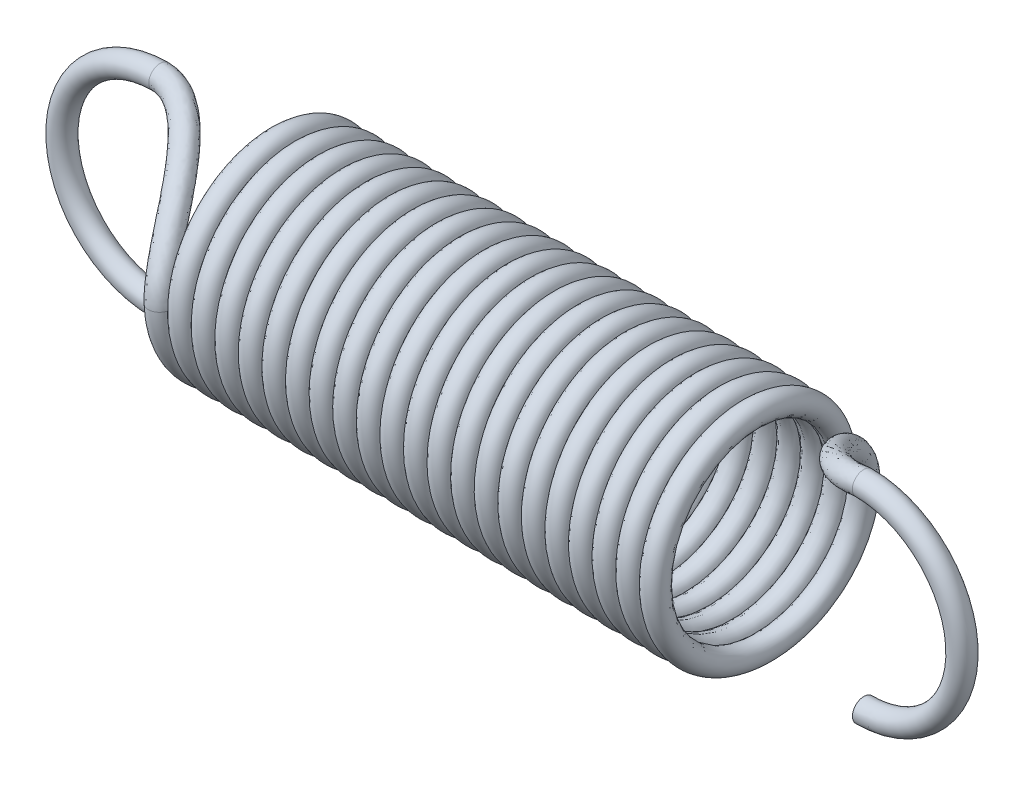
SolidWorks part; units mm, degrees
note: '?' marks a value the reader was unsure of.
ref_plane "Front Plane" through (0, 0, 0) normal (0, 0, 1) x (1, 0, 0)
ref_plane "Top Plane" through (0, 0, 0) normal (0, 1, 0) x (1, 0, 0)
ref_plane "Right Plane" through (0, 0, 0) normal (1, 0, 0) x (0, 0, -1)
sketch "Sketch1" plane through (0, 0, 0) normal (0, 0, 1) x (1, 0, 0)
  line L0 (-13.3604, 0) -> (13.3604, 0) construction
  line L1 (-13.3604, 3.175) -> (-13.3604, -3.175) construction
  line L2 (-13.3604, 0) -> (-12.7, 0) construction
  line L3 (-13.3604, 0) -> (37.4396, 0) construction
  line L5 (-13.3604, -3.175) -> (-13.3604, 3.175) construction
  line L6 (13.3604, 0) -> (-13.3604, 0) construction
  line L7 (37.4396, 0) -> (-13.3604, 0) construction
sketch "Sketch2" plane through (0, 0, 0) normal (0, 0, 1) x (1, 0, 0)
  line L0 (-13.3604, 0) -> (13.3604, 0) construction
  line L1 (-10.1854, 3.175) -> (10.1854, 3.175) construction
  line L2 (-10.1854, 2.5146) -> (10.1854, 2.5146) construction
  line L3 (-10.1854, 0) -> (-10.1854, -2.8448) construction
  line L5 (-10.1854, 2.5146) -> (-10.1854, 3.175) construction
  line L6 (-7.6708, 0) -> (-7.0104, 0) construction
  line L7 (7.6708, 0) -> (7.0104, 0) construction
  circle A0 centre (-10.1854, 0) radius 3.175 construction
  circle A1 centre (-10.1854, 0) radius 2.5146 construction
  arc A2 (-10.1854, 2.8448) -> (-10.1854, -2.8448) centre (-10.1854, 0) ccw
  circle A3 centre (10.1854, 0) radius 3.175 construction
  circle A4 centre (10.1854, 0) radius 2.5146 construction
  point P14 (-10.1854, -2.5146)
  point P24 (-7.3406, 0)
  point P25 (7.3406, 0)
  dimension "D1" = 90
  dimension "D2" = 14.6812
ref_plane "Plane1" through (-7.3406, 0, 0) normal (1, 0, 0) x (0, 0, -1)
sketch "Sketch3" plane through (-7.3406, 0, 0) normal (1, 0, 0) x (0, 0, -1)
  circle A0 centre (0, 0) radius 2.8448
  point P3 (0, 2.8448)
  point P4 (-2.8448, 0)
curve "Helix/Spiral1" pitch 0.6828 height 14.6812 turns 21.5
sketch "Sketch4" plane through (0, 0, 0) normal (0, 0, 1) x (1, 0, 0)
  line L0 (0, 0) -> (0, 3.175) construction
  line L1 (-10.1854, 3.175) -> (10.1854, 3.175) construction
  line L2 (10.1854, 2.5146) -> (10.1854, 3.175) construction
  arc A0 (-10.1854, 2.8448) -> (-10.1854, -2.8448) centre (-10.1854, 0) ccw construction
  arc A1 (-10.1854, 2.8448) -> (-10.1854, -2.8448) centre (-10.1854, 0) ccw construction
  arc A4 (10.1854, 2.8448) -> (10.1854, -2.8448) centre (10.1854, 0) cw
sketch "Sketch5" plane through (0, 0, 0) normal (0, 1, 0) x (1, 0, 0)
  line L0 (-7.3406, 0) -> (-7.3406, -2.8448) construction
  line L1 (-10.1854, 0) -> (-10.1854, -2.8448) construction
  line L3 (7.3406, 0) -> (7.3406, 2.8448) construction
  point P8 (-7.3406, -2.8448)
  point P9 (7.3406, 2.8448)
ref_plane "Plane2" through (-10.1854, 0, 0) normal (-1, 0, 0) x (0, 0, 1)
sketch3d "3DSketch1"
  arc A0 (-10.1854, 2.8448, 0) -> (-10.1854, -2.8448, 0) centre (-10.1854, 0, 0) ccw construction
  arc A1 (-10.1854, 2.8448, 0) -> (-10.1854, -2.8448, 0) centre (-10.1854, 0, 0) ccw construction
  spline S0 degree 3 poles (-10.1854, 2.8448, 0) (-8.5979, 2.8448, 0) (-7.4012, 1.5863, 2.8449) (-7.3406, 0, 2.8448) knots 0 0 0 0 1 1 1 1
  spline S1 degree 3 poles (-7.3406, 0, 2.8448) (-7.3265, -0.37, 2.8448) (-7.2979, -1.1181, 2.6967) (-7.2553, -2.0637, 2.0639) (-7.2126, -2.6968, 1.117) (-7.1699, -2.9188, 0) (-7.1272, -2.6967, -1.117) (-7.0845, -2.0639, -2.0639) (-7.0419, -1.117, -2.6967) (-6.9992, 0, -2.9189) (-6.9565, 1.117, -2.6967) (-6.9138, 2.0639, -2.0639) (-6.8711, 2.6967, -1.117) (-6.8285, 2.9189, 0) (-6.7858, 2.6967, 1.117) (-6.7431, 2.0639, 2.0639) (-6.7004, 1.117, 2.6967) (-6.6578, 0, 2.9189) (-6.6151, -1.117, 2.6967) (-6.5724, -2.0639, 2.0639) (-6.5297, -2.6967, 1.117) (-6.487, -2.9189, 0) (-6.4444, -2.6967, -1.117) (-6.4017, -2.0639, -2.0639) (-6.359, -1.117, -2.6967) (-6.3163, 0, -2.9189) (-6.2737, 1.117, -2.6967) (-6.231, 2.0639, -2.0639) (-6.1883, 2.6967, -1.117) (-6.1456, 2.9189, 0) (-6.1029, 2.6967, 1.117) (-6.0603, 2.0639, 2.0639) (-6.0176, 1.117, 2.6967) (-5.9749, 0, 2.9189) (-5.9322, -1.117, 2.6967) (-5.8896, -2.0639, 2.0639) (-5.8469, -2.6967, 1.117) (-5.8042, -2.9189, 0) (-5.7615, -2.6967, -1.117) (-5.7188, -2.0639, -2.0639) (-5.6762, -1.117, -2.6967) (-5.6335, 0, -2.9189) (-5.5908, 1.117, -2.6967) (-5.5481, 2.0639, -2.0639) (-5.5054, 2.6967, -1.117) (-5.4628, 2.9189, 0) (-5.4201, 2.6967, 1.117) (-5.3774, 2.0639, 2.0639) (-5.3347, 1.117, 2.6967) (-5.2921, 0, 2.9189) (-5.2494, -1.117, 2.6967) (-5.2067, -2.0639, 2.0639) (-5.164, -2.6967, 1.117) (-5.1213, -2.9189, 0) (-5.0787, -2.6967, -1.117) (-5.036, -2.0639, -2.0639) (-4.9933, -1.117, -2.6967) (-4.9506, 0, -2.9189) (-4.908, 1.117, -2.6967) (-4.8653, 2.0639, -2.0639) (-4.8226, 2.6967, -1.117) (-4.7799, 2.9189, 0) (-4.7372, 2.6967, 1.117) (-4.6946, 2.0639, 2.0639) (-4.6519, 1.117, 2.6967) (-4.6092, 0, 2.9189) (-4.5665, -1.117, 2.6967) (-4.5239, -2.0639, 2.0639) (-4.4812, -2.6967, 1.117) (-4.4385, -2.9189, 0) (-4.3958, -2.6967, -1.117) (-4.3531, -2.0639, -2.0639) (-4.3105, -1.117, -2.6967) (-4.2678, 0, -2.9189) (-4.2251, 1.117, -2.6967) (-4.1824, 2.0639, -2.0639) (-4.1398, 2.6967, -1.117) (-4.0971, 2.9189, 0) (-4.0544, 2.6967, 1.117) (-4.0117, 2.0639, 2.0639) (-3.969, 1.117, 2.6967) (-3.9264, 0, 2.9189) (-3.8837, -1.117, 2.6967) (-3.841, -2.0639, 2.0639) (-3.7983, -2.6967, 1.117) (-3.7557, -2.9189, 0) (-3.713, -2.6967, -1.117) (-3.6703, -2.0639, -2.0639) (-3.6276, -1.117, -2.6967) (-3.5849, 0, -2.9189) (-3.5423, 1.117, -2.6967) (-3.4996, 2.0639, -2.0639) (-3.4569, 2.6967, -1.117) (-3.4142, 2.9189, 0) (-3.3716, 2.6967, 1.117) (-3.3289, 2.0639, 2.0639) (-3.2862, 1.117, 2.6967) (-3.2435, 0, 2.9189) (-3.2008, -1.117, 2.6967) (-3.1582, -2.0639, 2.0639) (-3.1155, -2.6967, 1.117) (-3.0728, -2.9189, 0) (-3.0301, -2.6967, -1.117) (-2.9875, -2.0639, -2.0639) (-2.9448, -1.117, -2.6967) (-2.9021, 0, -2.9189) (-2.8594, 1.117, -2.6967) (-2.8167, 2.0639, -2.0639) (-2.7741, 2.6967, -1.117) (-2.7314, 2.9189, 0) (-2.6887, 2.6967, 1.117) (-2.646, 2.0639, 2.0639) (-2.6034, 1.117, 2.6967) (-2.5607, 0, 2.9189) (-2.518, -1.117, 2.6967) (-2.4753, -2.0639, 2.0639) (-2.4326, -2.6967, 1.117) (-2.39, -2.9189, 0) (-2.3473, -2.6967, -1.117) (-2.3046, -2.0639, -2.0639) (-2.2619, -1.117, -2.6967) (-2.2193, 0, -2.9189) (-2.1766, 1.117, -2.6967) (-2.1339, 2.0639, -2.0639) (-2.0912, 2.6967, -1.117) (-2.0485, 2.9189, 0) (-2.0059, 2.6967, 1.117) (-1.9632, 2.0639, 2.0639) (-1.9205, 1.117, 2.6967) (-1.8778, 0, 2.9189) (-1.8351, -1.117, 2.6967) (-1.7925, -2.0639, 2.0639) (-1.7498, -2.6967, 1.117) (-1.7071, -2.9189, 0) (-1.6644, -2.6967, -1.117) (-1.6218, -2.0639, -2.0639) (-1.5791, -1.117, -2.6967) (-1.5364, 0, -2.9189) (-1.4937, 1.117, -2.6967) (-1.451, 2.0639, -2.0639) (-1.4084, 2.6967, -1.117) (-1.3657, 2.9189, 0) (-1.323, 2.6967, 1.117) (-1.2803, 2.0639, 2.0639) (-1.2377, 1.117, 2.6967) (-1.195, 0, 2.9189) (-1.1523, -1.117, 2.6967) (-1.1096, -2.0639, 2.0639) (-1.0669, -2.6967, 1.117) (-1.0243, -2.9189, 0) (-0.9816, -2.6967, -1.117) (-0.9389, -2.0639, -2.0639) (-0.8962, -1.117, -2.6967) (-0.8536, 0, -2.9189) (-0.8109, 1.117, -2.6967) (-0.7682, 2.0639, -2.0639) (-0.7255, 2.6967, -1.117) (-0.6828, 2.9189, 0) (-0.6402, 2.6967, 1.117) (-0.5975, 2.0639, 2.0639) (-0.5548, 1.117, 2.6967) (-0.5121, 0, 2.9189) (-0.4695, -1.117, 2.6967) (-0.4268, -2.0639, 2.0639) (-0.3841, -2.6967, 1.117) (-0.3414, -2.9189, 0) (-0.2987, -2.6967, -1.117) (-0.2561, -2.0639, -2.0639) (-0.2134, -1.117, -2.6967) (-0.1707, 0, -2.9189) (-0.128, 1.117, -2.6967) (-0.0854, 2.0639, -2.0639) (-0.0427, 2.6967, -1.117) (0, 2.9189, 0) (0.0427, 2.6967, 1.117) (0.0854, 2.0639, 2.0639) (0.128, 1.117, 2.6967) (0.1707, 0, 2.9189) (0.2134, -1.117, 2.6967) (0.2561, -2.0639, 2.0639) (0.2987, -2.6967, 1.117) (0.3414, -2.9189, 0) (0.3841, -2.6967, -1.117) (0.4268, -2.0639, -2.0639) (0.4695, -1.117, -2.6967) (0.5121, 0, -2.9189) (0.5548, 1.117, -2.6967) (0.5975, 2.0639, -2.0639) (0.6402, 2.6967, -1.117) (0.6828, 2.9189, 0) (0.7255, 2.6967, 1.117) (0.7682, 2.0639, 2.0639) (0.8109, 1.117, 2.6967) (0.8536, 0, 2.9189) (0.8962, -1.117, 2.6967) (0.9389, -2.0639, 2.0639) (0.9816, -2.6967, 1.117) (1.0243, -2.9189, 0) (1.0669, -2.6967, -1.117) (1.1096, -2.0639, -2.0639) (1.1523, -1.117, -2.6967) (1.195, 0, -2.9189) (1.2377, 1.117, -2.6967) (1.2803, 2.0639, -2.0639) (1.323, 2.6967, -1.117) (1.3657, 2.9189, 0) (1.4084, 2.6967, 1.117) (1.451, 2.0639, 2.0639) (1.4937, 1.117, 2.6967) (1.5364, 0, 2.9189) (1.5791, -1.117, 2.6967) (1.6218, -2.0639, 2.0639) (1.6644, -2.6967, 1.117) (1.7071, -2.9189, 0) (1.7498, -2.6967, -1.117) (1.7925, -2.0639, -2.0639) (1.8351, -1.117, -2.6967) (1.8778, 0, -2.9189) (1.9205, 1.117, -2.6967) (1.9632, 2.0639, -2.0639) (2.0059, 2.6967, -1.117) (2.0485, 2.9189, 0) (2.0912, 2.6967, 1.117) (2.1339, 2.0639, 2.0639) (2.1766, 1.117, 2.6967) (2.2193, 0, 2.9189) (2.2619, -1.117, 2.6967) (2.3046, -2.0639, 2.0639) (2.3473, -2.6967, 1.117) (2.39, -2.9189, 0) (2.4326, -2.6967, -1.117) (2.4753, -2.0639, -2.0639) (2.518, -1.117, -2.6967) (2.5607, 0, -2.9189) (2.6034, 1.117, -2.6967) (2.646, 2.0639, -2.0639) (2.6887, 2.6967, -1.117) (2.7314, 2.9189, 0) (2.7741, 2.6967, 1.117) (2.8167, 2.0639, 2.0639) (2.8594, 1.117, 2.6967) (2.9021, 0, 2.9189) (2.9448, -1.117, 2.6967) (2.9875, -2.0639, 2.0639) (3.0301, -2.6967, 1.117) (3.0728, -2.9189, 0) (3.1155, -2.6967, -1.117) (3.1582, -2.0639, -2.0639) (3.2008, -1.117, -2.6967) (3.2435, 0, -2.9189) (3.2862, 1.117, -2.6967) (3.3289, 2.0639, -2.0639) (3.3716, 2.6967, -1.117) (3.4142, 2.9189, 0) (3.4569, 2.6967, 1.117) (3.4996, 2.0639, 2.0639) (3.5423, 1.117, 2.6967) (3.5849, 0, 2.9189) (3.6276, -1.117, 2.6967) (3.6703, -2.0639, 2.0639) (3.713, -2.6967, 1.117) (3.7557, -2.9189, 0) (3.7983, -2.6967, -1.117) (3.841, -2.0639, -2.0639) (3.8837, -1.117, -2.6967) (3.9264, 0, -2.9189) (3.969, 1.117, -2.6967) (4.0117, 2.0639, -2.0639) (4.0544, 2.6967, -1.117) (4.0971, 2.9189, 0) (4.1398, 2.6967, 1.117) (4.1824, 2.0639, 2.0639) (4.2251, 1.117, 2.6967) (4.2678, 0, 2.9189) (4.3105, -1.117, 2.6967) (4.3531, -2.0639, 2.0639) (4.3958, -2.6967, 1.117) (4.4385, -2.9189, 0) (4.4812, -2.6967, -1.117) (4.5239, -2.0639, -2.0639) (4.5665, -1.117, -2.6967) (4.6092, 0, -2.9189) (4.6519, 1.117, -2.6967) (4.6946, 2.0639, -2.0639) (4.7372, 2.6967, -1.117) (4.7799, 2.9189, 0) (4.8226, 2.6967, 1.117) (4.8653, 2.0639, 2.0639) (4.908, 1.117, 2.6967) (4.9506, 0, 2.9189) (4.9933, -1.117, 2.6967) (5.036, -2.0639, 2.0639) (5.0787, -2.6967, 1.117) (5.1213, -2.9189, 0) (5.164, -2.6967, -1.117) (5.2067, -2.0639, -2.0639) (5.2494, -1.117, -2.6967) (5.2921, 0, -2.9189) (5.3347, 1.117, -2.6967) (5.3774, 2.0639, -2.0639) (5.4201, 2.6967, -1.117) (5.4628, 2.9189, 0) (5.5054, 2.6967, 1.117) (5.5481, 2.0639, 2.0639) (5.5908, 1.117, 2.6967) (5.6335, 0, 2.9189) (5.6762, -1.117, 2.6967) (5.7188, -2.0639, 2.0639) (5.7615, -2.6967, 1.117) (5.8042, -2.9189, 0) (5.8469, -2.6967, -1.117) (5.8896, -2.0639, -2.0639) (5.9322, -1.117, -2.6967) (5.9749, 0, -2.9189) (6.0176, 1.117, -2.6967) (6.0603, 2.0639, -2.0639) (6.1029, 2.6967, -1.117) (6.1456, 2.9189, 0) (6.1883, 2.6967, 1.117) (6.231, 2.0639, 2.0639) (6.2737, 1.117, 2.6967) (6.3163, 0, 2.9189) (6.359, -1.117, 2.6967) (6.4017, -2.0639, 2.0639) (6.4444, -2.6967, 1.117) (6.487, -2.9189, 0) (6.5297, -2.6967, -1.117) (6.5724, -2.0639, -2.0639) (6.6151, -1.117, -2.6967) (6.6578, 0, -2.9189) (6.7004, 1.117, -2.6967) (6.7431, 2.0639, -2.0639) (6.7858, 2.6967, -1.117) (6.8285, 2.9189, 0) (6.8711, 2.6967, 1.117) (6.9138, 2.0639, 2.0639) (6.9565, 1.117, 2.6967) (6.9992, 0, 2.9189) (7.0419, -1.117, 2.6967) (7.0845, -2.0639, 2.0639) (7.1272, -2.6967, 1.117) (7.1699, -2.9188, 0) (7.2126, -2.6968, -1.117) (7.2553, -2.0637, -2.0639) (7.2979, -1.1181, -2.6967) (7.3265, -0.37, -2.8448) (7.3406, 0, -2.8448) knots 0 0 0 0 0.002907 0.005814 0.008721 0.011628 0.014535 0.017442 0.020349 0.023256 0.026163 0.02907 0.031977 0.034884 0.037791 0.040698 0.043605 0.046512 0.049419 0.052326 0.055233 0.05814 0.061047 0.063953 0.06686 0.069767 0.072674 0.075581 0.078488 0.081395 0.084302 0.087209 0.090116 0.093023 0.09593 0.098837 0.101744 0.104651 0.107558 0.110465 0.113372 0.116279 0.119186 0.122093 0.125 0.127907 0.130814 0.133721 0.136628 0.139535 0.142442 0.145349 0.148256 0.151163 0.15407 0.156977 0.159884 0.162791 0.165698 0.168605 0.171512 0.174419 0.177326 0.180233 0.18314 0.186047 0.188953 0.19186 0.194767 0.197674 0.200581 0.203488 0.206395 0.209302 0.212209 0.215116 0.218023 0.22093 0.223837 0.226744 0.229651 0.232558 0.235465 0.238372 0.241279 0.244186 0.247093 0.25 0.252907 0.255814 0.258721 0.261628 0.264535 0.267442 0.270349 0.273256 0.276163 0.27907 0.281977 0.284884 0.287791 0.290698 0.293605 0.296512 0.299419 0.302326 0.305233 0.30814 0.311047 0.313953 0.31686 0.319767 0.322674 0.325581 0.328488 0.331395 0.334302 0.337209 0.340116 0.343023 0.34593 0.348837 0.351744 0.354651 0.357558 0.360465 0.363372 0.366279 0.369186 0.372093 0.375 0.377907 0.380814 0.383721 0.386628 0.389535 0.392442 0.395349 0.398256 0.401163 0.40407 0.406977 0.409884 0.412791 0.415698 0.418605 0.421512 0.424419 0.427326 0.430233 0.43314 0.436047 0.438953 0.44186 0.444767 0.447674 0.450581 0.453488 0.456395 0.459302 0.462209 0.465116 0.468023 0.47093 0.473837 0.476744 0.479651 0.482558 0.485465 0.488372 0.491279 0.494186 0.497093 0.5 0.502907 0.505814 0.508721 0.511628 0.514535 0.517442 0.520349 0.523256 0.526163 0.52907 0.531977 0.534884 0.537791 0.540698 0.543605 0.546512 0.549419 0.552326 0.555233 0.55814 0.561047 0.563953 0.56686 0.569767 0.572674 0.575581 0.578488 0.581395 0.584302 0.587209 0.590116 0.593023 0.59593 0.598837 0.601744 0.604651 0.607558 0.610465 0.613372 0.616279 0.619186 0.622093 0.625 0.627907 0.630814 0.633721 0.636628 0.639535 0.642442 0.645349 0.648256 0.651163 0.65407 0.656977 0.659884 0.662791 0.665698 0.668605 0.671512 0.674419 0.677326 0.680233 0.68314 0.686047 0.688953 0.69186 0.694767 0.697674 0.700581 0.703488 0.706395 0.709302 0.712209 0.715116 0.718023 0.72093 0.723837 0.726744 0.729651 0.732558 0.735465 0.738372 0.741279 0.744186 0.747093 0.75 0.752907 0.755814 0.758721 0.761628 0.764535 0.767442 0.770349 0.773256 0.776163 0.77907 0.781977 0.784884 0.787791 0.790698 0.793605 0.796512 0.799419 0.802326 0.805233 0.80814 0.811047 0.813953 0.81686 0.819767 0.822674 0.825581 0.828488 0.831395 0.834302 0.837209 0.840116 0.843023 0.84593 0.848837 0.851744 0.854651 0.857558 0.860465 0.863372 0.866279 0.869186 0.872093 0.875 0.877907 0.880814 0.883721 0.886628 0.889535 0.892442 0.895349 0.898256 0.901163 0.90407 0.906977 0.909884 0.912791 0.915698 0.918605 0.921512 0.924419 0.927326 0.930233 0.93314 0.936047 0.938953 0.94186 0.944767 0.947674 0.950581 0.953488 0.956395 0.959302 0.962209 0.965116 0.968023 0.97093 0.973837 0.976744 0.979651 0.982558 0.985465 0.988372 0.991279 0.994186 0.997093 1 1 1 1 construction
  point P8 (-10.1854, 0, 2.8448)
  point P13 (-10.1854, 0, 2.8448)
  dimension "D1" = 4.7625
  dimension "D2" = 4.7625
sketch3d "3DSketch2"
  arc A0 (10.1854, 2.8448, 0) -> (10.1854, -2.8448, 0) centre (10.1854, 0, 0) ccw construction
  spline S0 degree 3 poles (7.3406, 0, -2.8448) (7.3982, 1.507, -2.8448) (8.4029, 2.5846, 0) (10.106, 2.8448, 0) (10.1854, 2.8448, 0) knots 0 0 0 0 0.95 1 1 1 1
  spline S1 degree 3 poles (-7.3406, 0, 2.8448) (-7.3265, -0.37, 2.8448) (-7.2979, -1.1181, 2.6967) (-7.2553, -2.0637, 2.0639) (-7.2126, -2.6968, 1.117) (-7.1699, -2.9188, 0) (-7.1272, -2.6967, -1.117) (-7.0845, -2.0639, -2.0639) (-7.0419, -1.117, -2.6967) (-6.9992, 0, -2.9189) (-6.9565, 1.117, -2.6967) (-6.9138, 2.0639, -2.0639) (-6.8711, 2.6967, -1.117) (-6.8285, 2.9189, 0) (-6.7858, 2.6967, 1.117) (-6.7431, 2.0639, 2.0639) (-6.7004, 1.117, 2.6967) (-6.6578, 0, 2.9189) (-6.6151, -1.117, 2.6967) (-6.5724, -2.0639, 2.0639) (-6.5297, -2.6967, 1.117) (-6.487, -2.9189, 0) (-6.4444, -2.6967, -1.117) (-6.4017, -2.0639, -2.0639) (-6.359, -1.117, -2.6967) (-6.3163, 0, -2.9189) (-6.2737, 1.117, -2.6967) (-6.231, 2.0639, -2.0639) (-6.1883, 2.6967, -1.117) (-6.1456, 2.9189, 0) (-6.1029, 2.6967, 1.117) (-6.0603, 2.0639, 2.0639) (-6.0176, 1.117, 2.6967) (-5.9749, 0, 2.9189) (-5.9322, -1.117, 2.6967) (-5.8896, -2.0639, 2.0639) (-5.8469, -2.6967, 1.117) (-5.8042, -2.9189, 0) (-5.7615, -2.6967, -1.117) (-5.7188, -2.0639, -2.0639) (-5.6762, -1.117, -2.6967) (-5.6335, 0, -2.9189) (-5.5908, 1.117, -2.6967) (-5.5481, 2.0639, -2.0639) (-5.5054, 2.6967, -1.117) (-5.4628, 2.9189, 0) (-5.4201, 2.6967, 1.117) (-5.3774, 2.0639, 2.0639) (-5.3347, 1.117, 2.6967) (-5.2921, 0, 2.9189) (-5.2494, -1.117, 2.6967) (-5.2067, -2.0639, 2.0639) (-5.164, -2.6967, 1.117) (-5.1213, -2.9189, 0) (-5.0787, -2.6967, -1.117) (-5.036, -2.0639, -2.0639) (-4.9933, -1.117, -2.6967) (-4.9506, 0, -2.9189) (-4.908, 1.117, -2.6967) (-4.8653, 2.0639, -2.0639) (-4.8226, 2.6967, -1.117) (-4.7799, 2.9189, 0) (-4.7372, 2.6967, 1.117) (-4.6946, 2.0639, 2.0639) (-4.6519, 1.117, 2.6967) (-4.6092, 0, 2.9189) (-4.5665, -1.117, 2.6967) (-4.5239, -2.0639, 2.0639) (-4.4812, -2.6967, 1.117) (-4.4385, -2.9189, 0) (-4.3958, -2.6967, -1.117) (-4.3531, -2.0639, -2.0639) (-4.3105, -1.117, -2.6967) (-4.2678, 0, -2.9189) (-4.2251, 1.117, -2.6967) (-4.1824, 2.0639, -2.0639) (-4.1398, 2.6967, -1.117) (-4.0971, 2.9189, 0) (-4.0544, 2.6967, 1.117) (-4.0117, 2.0639, 2.0639) (-3.969, 1.117, 2.6967) (-3.9264, 0, 2.9189) (-3.8837, -1.117, 2.6967) (-3.841, -2.0639, 2.0639) (-3.7983, -2.6967, 1.117) (-3.7557, -2.9189, 0) (-3.713, -2.6967, -1.117) (-3.6703, -2.0639, -2.0639) (-3.6276, -1.117, -2.6967) (-3.5849, 0, -2.9189) (-3.5423, 1.117, -2.6967) (-3.4996, 2.0639, -2.0639) (-3.4569, 2.6967, -1.117) (-3.4142, 2.9189, 0) (-3.3716, 2.6967, 1.117) (-3.3289, 2.0639, 2.0639) (-3.2862, 1.117, 2.6967) (-3.2435, 0, 2.9189) (-3.2008, -1.117, 2.6967) (-3.1582, -2.0639, 2.0639) (-3.1155, -2.6967, 1.117) (-3.0728, -2.9189, 0) (-3.0301, -2.6967, -1.117) (-2.9875, -2.0639, -2.0639) (-2.9448, -1.117, -2.6967) (-2.9021, 0, -2.9189) (-2.8594, 1.117, -2.6967) (-2.8167, 2.0639, -2.0639) (-2.7741, 2.6967, -1.117) (-2.7314, 2.9189, 0) (-2.6887, 2.6967, 1.117) (-2.646, 2.0639, 2.0639) (-2.6034, 1.117, 2.6967) (-2.5607, 0, 2.9189) (-2.518, -1.117, 2.6967) (-2.4753, -2.0639, 2.0639) (-2.4326, -2.6967, 1.117) (-2.39, -2.9189, 0) (-2.3473, -2.6967, -1.117) (-2.3046, -2.0639, -2.0639) (-2.2619, -1.117, -2.6967) (-2.2193, 0, -2.9189) (-2.1766, 1.117, -2.6967) (-2.1339, 2.0639, -2.0639) (-2.0912, 2.6967, -1.117) (-2.0485, 2.9189, 0) (-2.0059, 2.6967, 1.117) (-1.9632, 2.0639, 2.0639) (-1.9205, 1.117, 2.6967) (-1.8778, 0, 2.9189) (-1.8351, -1.117, 2.6967) (-1.7925, -2.0639, 2.0639) (-1.7498, -2.6967, 1.117) (-1.7071, -2.9189, 0) (-1.6644, -2.6967, -1.117) (-1.6218, -2.0639, -2.0639) (-1.5791, -1.117, -2.6967) (-1.5364, 0, -2.9189) (-1.4937, 1.117, -2.6967) (-1.451, 2.0639, -2.0639) (-1.4084, 2.6967, -1.117) (-1.3657, 2.9189, 0) (-1.323, 2.6967, 1.117) (-1.2803, 2.0639, 2.0639) (-1.2377, 1.117, 2.6967) (-1.195, 0, 2.9189) (-1.1523, -1.117, 2.6967) (-1.1096, -2.0639, 2.0639) (-1.0669, -2.6967, 1.117) (-1.0243, -2.9189, 0) (-0.9816, -2.6967, -1.117) (-0.9389, -2.0639, -2.0639) (-0.8962, -1.117, -2.6967) (-0.8536, 0, -2.9189) (-0.8109, 1.117, -2.6967) (-0.7682, 2.0639, -2.0639) (-0.7255, 2.6967, -1.117) (-0.6828, 2.9189, 0) (-0.6402, 2.6967, 1.117) (-0.5975, 2.0639, 2.0639) (-0.5548, 1.117, 2.6967) (-0.5121, 0, 2.9189) (-0.4695, -1.117, 2.6967) (-0.4268, -2.0639, 2.0639) (-0.3841, -2.6967, 1.117) (-0.3414, -2.9189, 0) (-0.2987, -2.6967, -1.117) (-0.2561, -2.0639, -2.0639) (-0.2134, -1.117, -2.6967) (-0.1707, 0, -2.9189) (-0.128, 1.117, -2.6967) (-0.0854, 2.0639, -2.0639) (-0.0427, 2.6967, -1.117) (0, 2.9189, 0) (0.0427, 2.6967, 1.117) (0.0854, 2.0639, 2.0639) (0.128, 1.117, 2.6967) (0.1707, 0, 2.9189) (0.2134, -1.117, 2.6967) (0.2561, -2.0639, 2.0639) (0.2987, -2.6967, 1.117) (0.3414, -2.9189, 0) (0.3841, -2.6967, -1.117) (0.4268, -2.0639, -2.0639) (0.4695, -1.117, -2.6967) (0.5121, 0, -2.9189) (0.5548, 1.117, -2.6967) (0.5975, 2.0639, -2.0639) (0.6402, 2.6967, -1.117) (0.6828, 2.9189, 0) (0.7255, 2.6967, 1.117) (0.7682, 2.0639, 2.0639) (0.8109, 1.117, 2.6967) (0.8536, 0, 2.9189) (0.8962, -1.117, 2.6967) (0.9389, -2.0639, 2.0639) (0.9816, -2.6967, 1.117) (1.0243, -2.9189, 0) (1.0669, -2.6967, -1.117) (1.1096, -2.0639, -2.0639) (1.1523, -1.117, -2.6967) (1.195, 0, -2.9189) (1.2377, 1.117, -2.6967) (1.2803, 2.0639, -2.0639) (1.323, 2.6967, -1.117) (1.3657, 2.9189, 0) (1.4084, 2.6967, 1.117) (1.451, 2.0639, 2.0639) (1.4937, 1.117, 2.6967) (1.5364, 0, 2.9189) (1.5791, -1.117, 2.6967) (1.6218, -2.0639, 2.0639) (1.6644, -2.6967, 1.117) (1.7071, -2.9189, 0) (1.7498, -2.6967, -1.117) (1.7925, -2.0639, -2.0639) (1.8351, -1.117, -2.6967) (1.8778, 0, -2.9189) (1.9205, 1.117, -2.6967) (1.9632, 2.0639, -2.0639) (2.0059, 2.6967, -1.117) (2.0485, 2.9189, 0) (2.0912, 2.6967, 1.117) (2.1339, 2.0639, 2.0639) (2.1766, 1.117, 2.6967) (2.2193, 0, 2.9189) (2.2619, -1.117, 2.6967) (2.3046, -2.0639, 2.0639) (2.3473, -2.6967, 1.117) (2.39, -2.9189, 0) (2.4326, -2.6967, -1.117) (2.4753, -2.0639, -2.0639) (2.518, -1.117, -2.6967) (2.5607, 0, -2.9189) (2.6034, 1.117, -2.6967) (2.646, 2.0639, -2.0639) (2.6887, 2.6967, -1.117) (2.7314, 2.9189, 0) (2.7741, 2.6967, 1.117) (2.8167, 2.0639, 2.0639) (2.8594, 1.117, 2.6967) (2.9021, 0, 2.9189) (2.9448, -1.117, 2.6967) (2.9875, -2.0639, 2.0639) (3.0301, -2.6967, 1.117) (3.0728, -2.9189, 0) (3.1155, -2.6967, -1.117) (3.1582, -2.0639, -2.0639) (3.2008, -1.117, -2.6967) (3.2435, 0, -2.9189) (3.2862, 1.117, -2.6967) (3.3289, 2.0639, -2.0639) (3.3716, 2.6967, -1.117) (3.4142, 2.9189, 0) (3.4569, 2.6967, 1.117) (3.4996, 2.0639, 2.0639) (3.5423, 1.117, 2.6967) (3.5849, 0, 2.9189) (3.6276, -1.117, 2.6967) (3.6703, -2.0639, 2.0639) (3.713, -2.6967, 1.117) (3.7557, -2.9189, 0) (3.7983, -2.6967, -1.117) (3.841, -2.0639, -2.0639) (3.8837, -1.117, -2.6967) (3.9264, 0, -2.9189) (3.969, 1.117, -2.6967) (4.0117, 2.0639, -2.0639) (4.0544, 2.6967, -1.117) (4.0971, 2.9189, 0) (4.1398, 2.6967, 1.117) (4.1824, 2.0639, 2.0639) (4.2251, 1.117, 2.6967) (4.2678, 0, 2.9189) (4.3105, -1.117, 2.6967) (4.3531, -2.0639, 2.0639) (4.3958, -2.6967, 1.117) (4.4385, -2.9189, 0) (4.4812, -2.6967, -1.117) (4.5239, -2.0639, -2.0639) (4.5665, -1.117, -2.6967) (4.6092, 0, -2.9189) (4.6519, 1.117, -2.6967) (4.6946, 2.0639, -2.0639) (4.7372, 2.6967, -1.117) (4.7799, 2.9189, 0) (4.8226, 2.6967, 1.117) (4.8653, 2.0639, 2.0639) (4.908, 1.117, 2.6967) (4.9506, 0, 2.9189) (4.9933, -1.117, 2.6967) (5.036, -2.0639, 2.0639) (5.0787, -2.6967, 1.117) (5.1213, -2.9189, 0) (5.164, -2.6967, -1.117) (5.2067, -2.0639, -2.0639) (5.2494, -1.117, -2.6967) (5.2921, 0, -2.9189) (5.3347, 1.117, -2.6967) (5.3774, 2.0639, -2.0639) (5.4201, 2.6967, -1.117) (5.4628, 2.9189, 0) (5.5054, 2.6967, 1.117) (5.5481, 2.0639, 2.0639) (5.5908, 1.117, 2.6967) (5.6335, 0, 2.9189) (5.6762, -1.117, 2.6967) (5.7188, -2.0639, 2.0639) (5.7615, -2.6967, 1.117) (5.8042, -2.9189, 0) (5.8469, -2.6967, -1.117) (5.8896, -2.0639, -2.0639) (5.9322, -1.117, -2.6967) (5.9749, 0, -2.9189) (6.0176, 1.117, -2.6967) (6.0603, 2.0639, -2.0639) (6.1029, 2.6967, -1.117) (6.1456, 2.9189, 0) (6.1883, 2.6967, 1.117) (6.231, 2.0639, 2.0639) (6.2737, 1.117, 2.6967) (6.3163, 0, 2.9189) (6.359, -1.117, 2.6967) (6.4017, -2.0639, 2.0639) (6.4444, -2.6967, 1.117) (6.487, -2.9189, 0) (6.5297, -2.6967, -1.117) (6.5724, -2.0639, -2.0639) (6.6151, -1.117, -2.6967) (6.6578, 0, -2.9189) (6.7004, 1.117, -2.6967) (6.7431, 2.0639, -2.0639) (6.7858, 2.6967, -1.117) (6.8285, 2.9189, 0) (6.8711, 2.6967, 1.117) (6.9138, 2.0639, 2.0639) (6.9565, 1.117, 2.6967) (6.9992, 0, 2.9189) (7.0419, -1.117, 2.6967) (7.0845, -2.0639, 2.0639) (7.1272, -2.6967, 1.117) (7.1699, -2.9188, 0) (7.2126, -2.6968, -1.117) (7.2553, -2.0637, -2.0639) (7.2979, -1.1181, -2.6967) (7.3265, -0.37, -2.8448) (7.3406, 0, -2.8448) knots 0 0 0 0 0.002907 0.005814 0.008721 0.011628 0.014535 0.017442 0.020349 0.023256 0.026163 0.02907 0.031977 0.034884 0.037791 0.040698 0.043605 0.046512 0.049419 0.052326 0.055233 0.05814 0.061047 0.063953 0.06686 0.069767 0.072674 0.075581 0.078488 0.081395 0.084302 0.087209 0.090116 0.093023 0.09593 0.098837 0.101744 0.104651 0.107558 0.110465 0.113372 0.116279 0.119186 0.122093 0.125 0.127907 0.130814 0.133721 0.136628 0.139535 0.142442 0.145349 0.148256 0.151163 0.15407 0.156977 0.159884 0.162791 0.165698 0.168605 0.171512 0.174419 0.177326 0.180233 0.18314 0.186047 0.188953 0.19186 0.194767 0.197674 0.200581 0.203488 0.206395 0.209302 0.212209 0.215116 0.218023 0.22093 0.223837 0.226744 0.229651 0.232558 0.235465 0.238372 0.241279 0.244186 0.247093 0.25 0.252907 0.255814 0.258721 0.261628 0.264535 0.267442 0.270349 0.273256 0.276163 0.27907 0.281977 0.284884 0.287791 0.290698 0.293605 0.296512 0.299419 0.302326 0.305233 0.30814 0.311047 0.313953 0.31686 0.319767 0.322674 0.325581 0.328488 0.331395 0.334302 0.337209 0.340116 0.343023 0.34593 0.348837 0.351744 0.354651 0.357558 0.360465 0.363372 0.366279 0.369186 0.372093 0.375 0.377907 0.380814 0.383721 0.386628 0.389535 0.392442 0.395349 0.398256 0.401163 0.40407 0.406977 0.409884 0.412791 0.415698 0.418605 0.421512 0.424419 0.427326 0.430233 0.43314 0.436047 0.438953 0.44186 0.444767 0.447674 0.450581 0.453488 0.456395 0.459302 0.462209 0.465116 0.468023 0.47093 0.473837 0.476744 0.479651 0.482558 0.485465 0.488372 0.491279 0.494186 0.497093 0.5 0.502907 0.505814 0.508721 0.511628 0.514535 0.517442 0.520349 0.523256 0.526163 0.52907 0.531977 0.534884 0.537791 0.540698 0.543605 0.546512 0.549419 0.552326 0.555233 0.55814 0.561047 0.563953 0.56686 0.569767 0.572674 0.575581 0.578488 0.581395 0.584302 0.587209 0.590116 0.593023 0.59593 0.598837 0.601744 0.604651 0.607558 0.610465 0.613372 0.616279 0.619186 0.622093 0.625 0.627907 0.630814 0.633721 0.636628 0.639535 0.642442 0.645349 0.648256 0.651163 0.65407 0.656977 0.659884 0.662791 0.665698 0.668605 0.671512 0.674419 0.677326 0.680233 0.68314 0.686047 0.688953 0.69186 0.694767 0.697674 0.700581 0.703488 0.706395 0.709302 0.712209 0.715116 0.718023 0.72093 0.723837 0.726744 0.729651 0.732558 0.735465 0.738372 0.741279 0.744186 0.747093 0.75 0.752907 0.755814 0.758721 0.761628 0.764535 0.767442 0.770349 0.773256 0.776163 0.77907 0.781977 0.784884 0.787791 0.790698 0.793605 0.796512 0.799419 0.802326 0.805233 0.80814 0.811047 0.813953 0.81686 0.819767 0.822674 0.825581 0.828488 0.831395 0.834302 0.837209 0.840116 0.843023 0.84593 0.848837 0.851744 0.854651 0.857558 0.860465 0.863372 0.866279 0.869186 0.872093 0.875 0.877907 0.880814 0.883721 0.886628 0.889535 0.892442 0.895349 0.898256 0.901163 0.90407 0.906977 0.909884 0.912791 0.915698 0.918605 0.921512 0.924419 0.927326 0.930233 0.93314 0.936047 0.938953 0.94186 0.944767 0.947674 0.950581 0.953488 0.956395 0.959302 0.962209 0.965116 0.968023 0.97093 0.973837 0.976744 0.979651 0.982558 0.985465 0.988372 0.991279 0.994186 0.997093 1 1 1 1 construction
  point P8 (10.1854, 0, -2.8448)
  dimension "D1" = 4.7625
  dimension "D2" = 4.7625
curve "CompCurve1"
sketch "Sketch6" plane through (-10.1854, 0, 0) normal (-1, 0, 0) x (0, 0, 1)
  circle A0 centre (0, -2.8448) radius 0.3302
sweep "Sweep1" add profiles "Sketch6" path "CompCurve1"
sketch "Sketch7" plane through (0, 0, 0) normal (0, 0, 1) x (1, 0, 0)
  line L0 (12.7, 0) -> (-12.7, 0) construction
  line L1 (12.7, 3.175) -> (-12.7, 3.175) construction
  line L2 (0, 3.175) -> (0, 0) construction
  line L3 (-12.7, -3.175) -> (12.7, -3.175) construction
  line L4 (0, 0) -> (0, -3.175) construction
  arc A1 (-10.1854, 2.5146) -> (-10.1854, -2.5146) centre (-10.1854, 0) ccw construction
  circle A2 centre (10.1854, 0) radius 2.5146 construction
  point P9 (12.7, 0)
  point P14 (12.7, 3.175)
  point P16 (-12.7, 3.175)
  point P20 (12.7, -3.175)
  point P21 (-12.7, -3.175)
sketch "Sketch9" plane through (10.1855, -0.0003, 0.0005) normal (-1, 0, 0) x (0, 1, -0.0001)
  circle A0 centre (-2.8445, 0.0007) radius 0.4953
  circle A1 centre (-2.8445, 0.0007) radius 0.3302 construction
  dimension "D1" = 0.9906
extrude "Cut-Extrude1" cut sketch "Sketch9" against normal blind 0.0025
sketch "Sketch10" plane through (0, 0, 0) normal (0, 0, 1) x (1, 0, 0)
  line L0 (-13.3604, 0) -> (-12.7, 0) construction
  line L1 (13.3604, 0) -> (12.7, 0) construction
  circle A0 centre (-10.1854, 0) radius 3.175 construction
  circle A1 centre (-10.1854, 0) radius 2.5146 construction
  circle A2 centre (10.1854, 0) radius 3.175 construction
  circle A3 centre (10.1854, 0) radius 2.5146 construction
  point P13 (13.0302, 0)
  point P14 (-13.0302, 0)
ref_axis "Axis1" through (-13.0302, -11.1162, 0) along (0, 1, 0)?
ref_axis "Axis2" through (13.0302, -9.8555, 0) along (0, 1, 0)?
ref_axis "Axis3" through (-40.0159, 0, 0) along (1, 0, 0)?
equation "\"D3@Helix/Spiral1\" = \"D2@Sketch2\""
equation "\"D1@3DSketch1\" = \"Spring OD@Sketch1\" * 3 / 4"
equation "\"D2@3DSketch1\" = \"D1@3DSketch1\""
equation "\"D1@3DSketch2\" = \"D1@3DSketch1\""
equation "\"D2@3DSketch2\" = \"D1@3DSketch2\""
equation "\"D1@Sketch9\"=\"Wire OD@Sketch1\" * 1.5"
